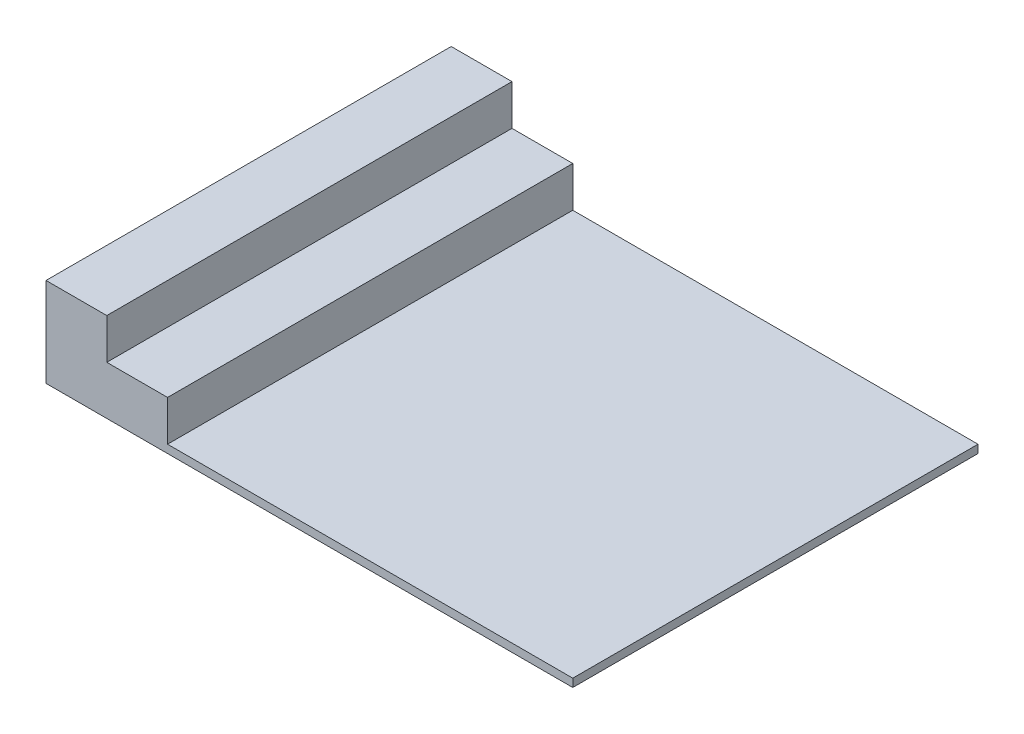
SolidWorks part; units mm, degrees
ref_plane "Plano frontal" through (0, 0, 0) normal (0, 0, 1) x (1, 0, 0)
ref_plane "Plano superior" through (0, 0, 0) normal (0, 1, 0) x (1, 0, 0)
ref_plane "Plano direito" through (0, 0, 0) normal (1, 0, 0) x (0, 0, -1)
sketch "Esboço1" plane through (0, 0, 0) normal (0, 0, 1) x (1, 0, 0)
  line L0 (223.4897, -121.4835) -> (-776.5103, -121.4835)
  line L1 (-776.5103, -121.4835) -> (-776.5103, -21.4835)
  line L2 (-776.5103, -21.4835) -> (-926.5103, -21.4835)
  line L4 (-840.2466, -141.4835) -> (223.4897, -141.4835)
  line L5 (223.4897, -141.4835) -> (223.4897, -121.4835)
  line L6 (-926.5103, -21.4835) -> (-926.5103, 78.5165)
  line L7 (-926.5103, 78.5165) -> (-1076.5103, 78.5165)
  line L8 (-1076.5103, 78.5165) -> (-1076.5103, -141.4835)
  line L9 (-1076.5103, -141.4835) -> (-840.2466, -141.4835)
  dimension "D1" = 1000
  dimension "D2" = 100
  dimension "D3" = 20
  dimension "D4" = 200
  dimension "D5" = 150
  dimension "D6" = 150
extrude "Ressalto-extrusão1" add sketch "Esboço1" along normal blind 1000
